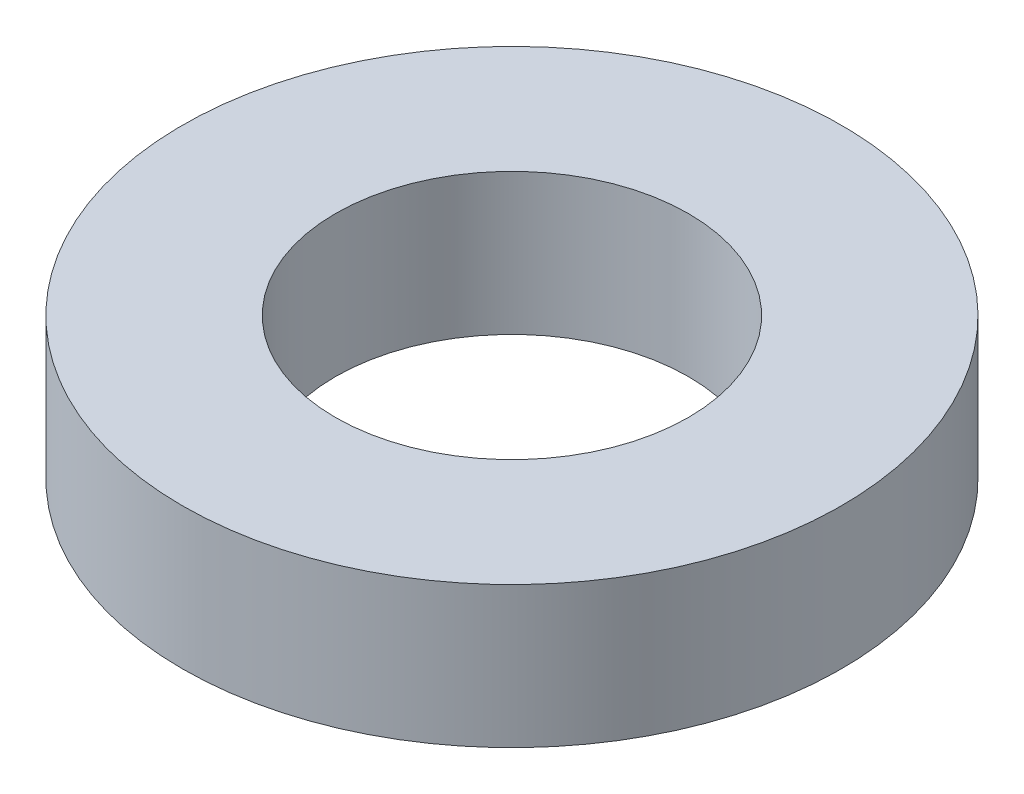
SolidWorks part; units mm, degrees
ref_plane "Front Plane" through (0, 0, 0) normal (0, 0, 1) x (1, 0, 0)
ref_plane "Top Plane" through (0, 0, 0) normal (0, 1, 0) x (1, 0, 0)
ref_plane "Right Plane" through (0, 0, 0) normal (1, 0, 0) x (0, 0, -1)
sketch "Sketch1" plane through (0, 0, 0) normal (0, 1, 0) x (1, 0, 0)
  circle A0 centre (0, 0) radius 70
  dimension "FLANGE_OD" = 140
extrude "Boss-Extrude1" add sketch "Sketch1" along normal blind 30
sketch "Sketch2" plane through (0, 0, 0) normal (0, 1, 0) x (1, 0, 0)
  circle A0 centre (0, 0) radius 37.5
  dimension "BORE_D" = 75
extrude "Cut-Extrude1" cut sketch "Sketch2" along normal through all
sketch "Sketch3" plane through (0, 30, 0) normal (0, 1, 0) x (1, 0, 0)
  circle A0 centre (0, 0) radius 28.8309 construction
  circle A1 centre (-28.8309, 0) radius 5.2972
  dimension "BOLT_D" = 10.5944
  dimension "BOLT_PCD" = 57.6619
extrude "Cut-Extrude2" cut sketch "Sketch3" against normal blind 25.5322 rebuild error yes
pattern_circular "CirPattern1" count 5 over 360 rebuild error yes
